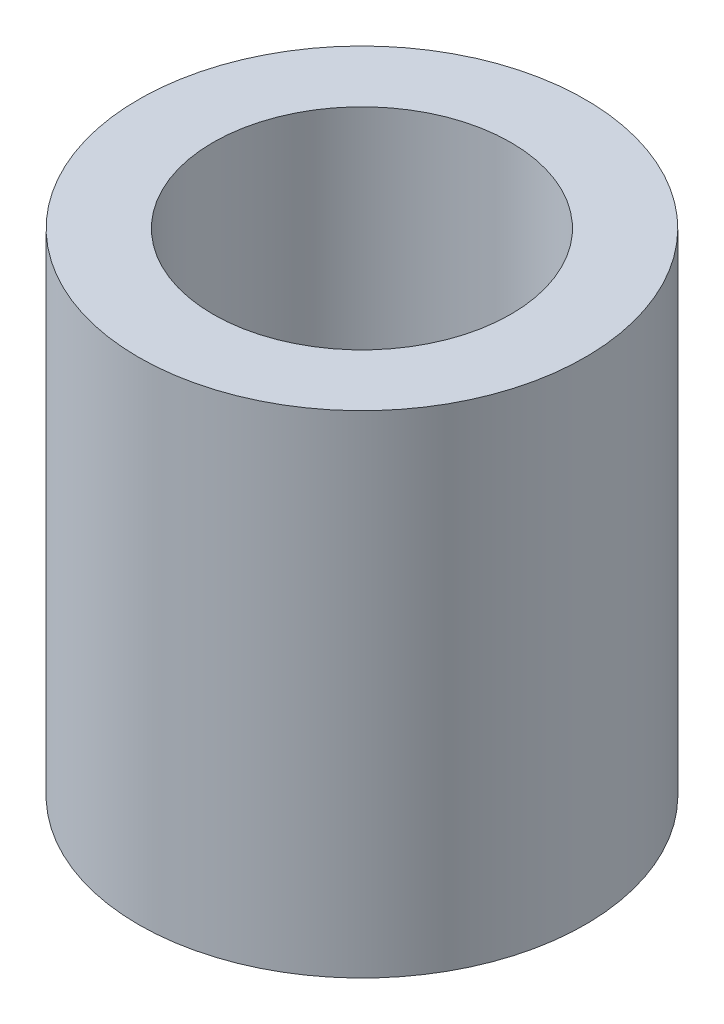
SolidWorks part; units mm, degrees
ref_plane "Plano frontal" through (0, 0, 0) normal (0, 0, 1) x (1, 0, 0)
ref_plane "Plano superior" through (0, 0, 0) normal (0, 1, 0) x (1, 0, 0)
ref_plane "Plano direito" through (0, 0, 0) normal (1, 0, 0) x (0, 0, -1)
sketch "Esboço2" plane through (0, 0, 0) normal (0, 1, 0) x (1, 0, 0)
  circle A0 centre (0, 0) radius 1.5
  circle A1 centre (0, 0) radius 1
  dimension "D1" = 3
  dimension "D2" = 2
extrude "Ressalto-extrusão1" add sketch "Esboço2" along normal blind 3.3 contours A0 A1 region at (-1.4576, 0, 0)
